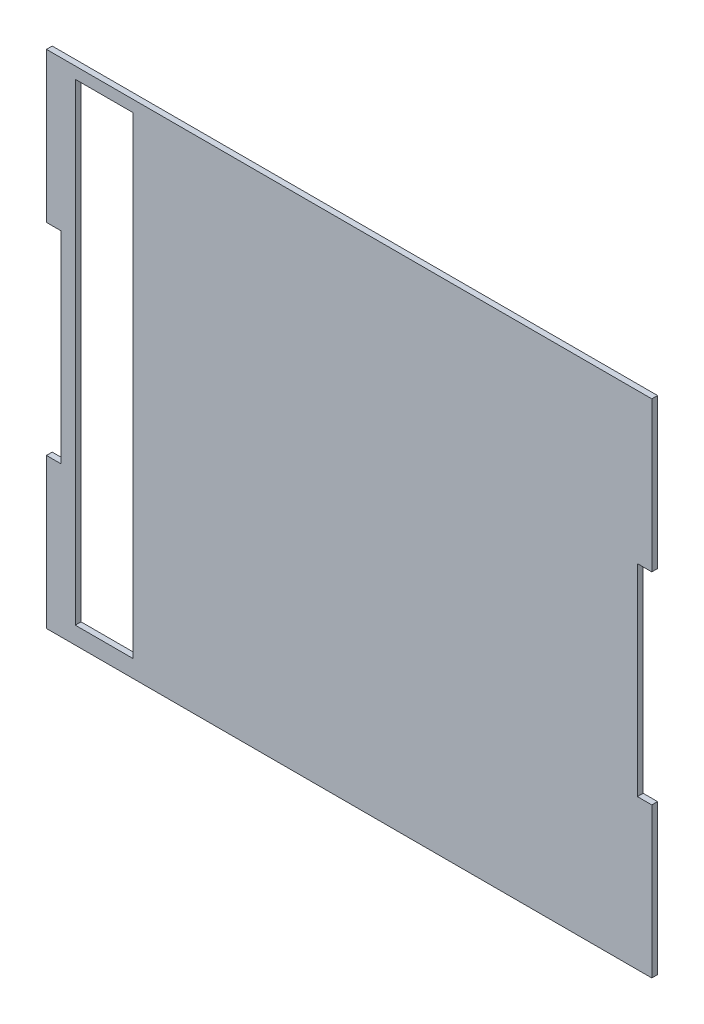
SolidWorks part; units mm, degrees
ref_plane "前视基准面" through (0, 0, 0) normal (0, 0, 1) x (1, 0, 0)
ref_plane "上视基准面" through (0, 0, 0) normal (0, 1, 0) x (1, 0, 0)
ref_plane "右视基准面" through (0, 0, 0) normal (1, 0, 0) x (0, 0, -1)
sketch "草图1" plane through (0, 0, 0) normal (0, 0, 1) x (1, 0, 0)
  line L48 (104.5, 35) -> (104.5, 87)
  line L49 (104.5, 87) -> (-105.5, 87)
  line L54 (-105.5, 35) -> (-105.5, 87)
  line L55 (-105.5, -35) -> (-105.5, -87)
  line L57 (104.5, -87) -> (-105.5, -87)
  line L58 (104.5, -35) -> (104.5, -87)
  line L63 (-105.5, 35) -> (-100.5, 35)
  line L64 (-100.5, 35) -> (-100.5, -35)
  line L65 (-100.5, -35) -> (-105.5, -35)
  line L66 (104.5, 35) -> (99.5, 35)
  line L67 (99.5, 35) -> (99.5, -35)
  line L69 (99.5, -35) -> (104.5, -35)
  line L71 (-95.5, 35) -> (-95.5, 83)
  line L72 (-95.5, 83) -> (-75.5, 83)
  line L73 (-75.5, 83) -> (-75.5, -81)
  line L74 (-75.5, -81) -> (-95.5, -81)
  line L75 (-95.5, -81) -> (-95.5, 35)
extrude "凸台-拉伸1" add sketch "草图1" along normal blind 2
